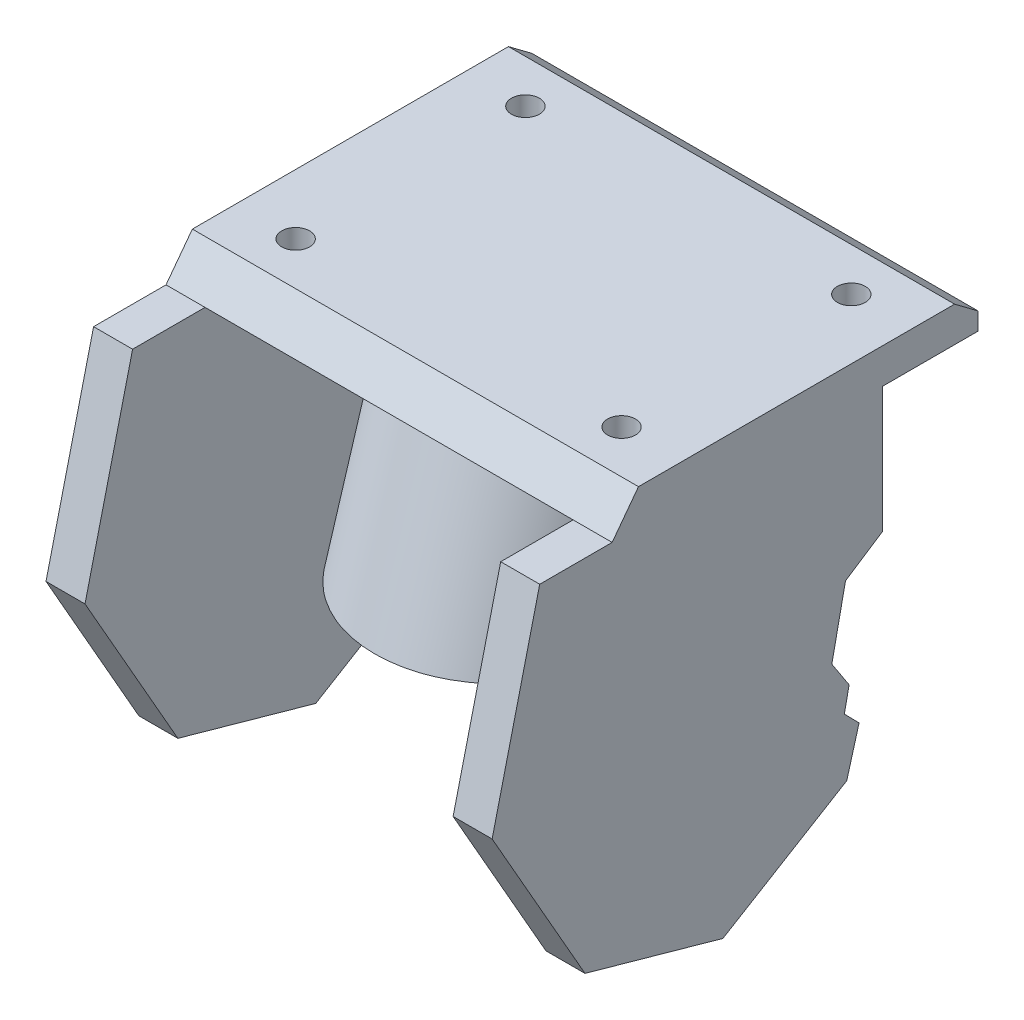
SolidWorks part; units mm, degrees
material "PF"
ref_plane "Front Plane" through (0, 0, 0) normal (0, 0, 1) x (1, 0, 0)
ref_plane "Top Plane" through (0, 0, 0) normal (0, 1, 0) x (1, 0, 0)
ref_plane "Right Plane" through (0, 0, 0) normal (1, 0, 0) x (0, 0, -1)
sketch "Sketch1" plane through (0, 0, 0) normal (1, 0, 0) x (0, 0, -1)
  line L0 (20.5, 54.5) -> (102.5, 54.5) construction
  line L1 (0, 14.4559) -> (3.413, 28.574)
  line L2 (3.413, 28.574) -> (8.6089, 28.574)
  line L3 (8.6089, 28.574) -> (10.4983, 31.0932)
  line L4 (10.4983, 31.0932) -> (33.1713, 31.0932)
  line L5 (33.1713, 31.0932) -> (34.8507, 29.8336)
  line L6 (34.8507, 29.8336) -> (34.8507, 28.574)
  line L7 (34.8507, 28.574) -> (28.0153, 28.574)
  line L8 (28.0153, 28.574) -> (28.0153, 19.5652)
  line L9 (28.0153, 19.5652) -> (25.3476, 17.8205)
  line L10 (25.3476, 17.8205) -> (24.3662, 13.1296)
  line L11 (24.3662, 13.1296) -> (25.6076, 11.2314)
  line L12 (25.6076, 11.2314) -> (25.2636, 9.5869)
  line L13 (25.2636, 9.5869) -> (26.3199, 8.5082)
  line L14 (26.3199, 8.5082) -> (25.4356, 5.3552)
  line L15 (25.4356, 5.3552) -> (16.5527, 0)
  line L16 (16.5527, 0) -> (6.6618, 2.7742)
  line L17 (6.6618, 2.7742) -> (0, 14.4559)
ref_plane "Plane1" through (32, 0, 0) normal (1, 0, 0) x (0, 0, -1)
sketch "Sketch2" plane through (32, 0, 0) normal (1, 0, 0) x (0, 0, -1)
  line L0 (20.5, 54.5) -> (102.5, 54.5) construction
  line L1 (0, 14.4559) -> (3.413, 28.574)
  line L2 (3.413, 28.574) -> (8.6089, 28.574)
  line L3 (8.6089, 28.574) -> (10.4983, 31.0932)
  line L4 (10.4983, 31.0932) -> (33.1713, 31.0932)
  line L5 (33.1713, 31.0932) -> (34.8507, 29.8336)
  line L6 (34.8507, 29.8336) -> (34.8507, 28.574)
  line L7 (34.8507, 28.574) -> (28.0153, 28.574)
  line L8 (28.0153, 28.574) -> (28.0153, 19.5652)
  line L9 (28.0153, 19.5652) -> (25.3476, 17.8205)
  line L10 (25.3476, 17.8205) -> (24.3662, 13.1296)
  line L11 (24.3662, 13.1296) -> (25.6076, 11.2314)
  line L12 (25.6076, 11.2314) -> (25.2636, 9.5869)
  line L13 (25.2636, 9.5869) -> (26.3199, 8.5082)
  line L14 (26.3199, 8.5082) -> (25.4356, 5.3552)
  line L15 (25.4356, 5.3552) -> (16.5527, 0)
  line L16 (16.5527, 0) -> (6.6618, 2.7742)
  line L17 (6.6618, 2.7742) -> (0, 14.4559)
loft "Loft1" add profiles "Sketch2", "Sketch1"
sketch "Sketch3" plane through (0, 0, 0) normal (0, 0, 1) x (1, 0, 0)
  line L0 (2.7986, 28.574) -> (29.2014, 28.574)
  line L2 (32, 28.574) -> (0, 28.574) construction
  line L3 (29.2014, 28.574) -> (29.2014, -1.5925)
  line L4 (29.2014, -1.5925) -> (2.7986, -1.5925)
  line L5 (2.7986, -1.5925) -> (2.7986, 28.574)
  point P3 (16, 28.574)
extrude "Cut-Extrude1" cut sketch "Sketch3" against normal blind 47
ref_plane "Plane2" through (0, 31.0932, 0) normal (0, 1, 0) x (1, 0, 0)
sketch "Sketch4" plane through (0, 31.0932, 0) normal (0, 1, 0) x (1, 0, 0)
  circle A0 centre (4.311, 30.0748) radius 1
ref_plane "Plane3" through (16, 0, 0) normal (1, 0, 0) x (0, 0, -1)
ref_plane "Plane4" through (0, 0, -21.8348) normal (0, 0, 1) x (1, 0, 0)
extrude "Cut-Extrude3" cut sketch "Sketch4" against normal blind 47 contours A0
mirror "Mirror3" about plane through (16, 0, 0) normal (1, 0, 0) of "Cut-Extrude3"
mirror "Mirror4" about plane through (0, 0, -21.8348) normal (0, 0, 1) of "Mirror3", "Cut-Extrude3"
ref_plane "Plane5" through (0, 28.574, 0) normal (0, -1, 0) x (-1, 0, 0)
sketch "Sketch5" plane through (0, 28.574, 0) normal (0, -1, 0) x (-1, 0, 0)
  line L0 (-9.0181, 24.1128) -> (-7.9524, 24.5482)
  line L1 (-23.2365, 24.1128) -> (-24.3022, 24.5482)
  arc A0 (-7.9524, 24.5482) -> (-24.3022, 24.5482) centre (-16.1273, 20.7977) cw
  arc A1 (-9.0181, 24.1128) -> (-23.2365, 24.1128) centre (-16.1273, 21.1033) cw
ref_plane "Plane6" through (0, 14.289, 0) normal (0, -1, 0) x (-1, 0, 0)
sketch "Sketch6" plane through (0, 14.289, 0) normal (0, -1, 0) x (-1, 0, 0)
  line L0 (-9.0181, 19.7616) -> (-7.9524, 20.1969)
  line L1 (-23.2365, 19.7616) -> (-24.3022, 20.1969)
  arc A0 (-7.9524, 20.1969) -> (-24.3022, 20.1969) centre (-16.1273, 16.4465) cw
  arc A1 (-9.0181, 19.7616) -> (-23.2365, 19.7616) centre (-16.1273, 16.7521) cw
  point P2 (-16.1273, 16.6282)
loft "Loft2" add profiles "Sketch6", "Sketch5"
